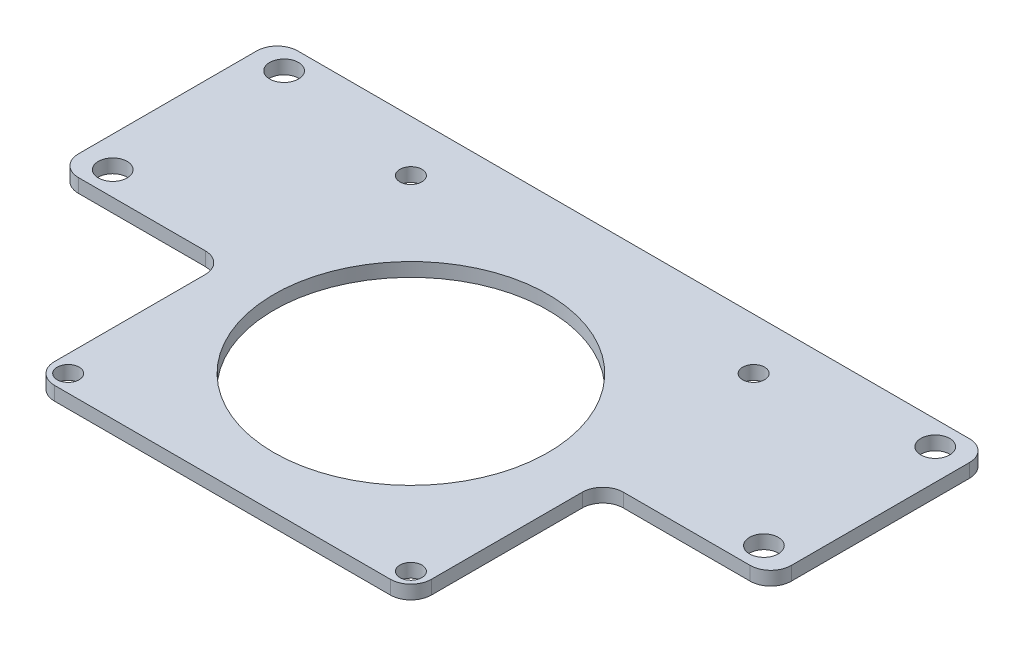
SolidWorks part; units mm, degrees
material "Thornel Mat VMA"
ref_plane "前视基准面" through (0, 0, 0) normal (0, 0, 1) x (1, 0, 0)
ref_plane "上视基准面" through (0, 0, 0) normal (0, 1, 0) x (1, 0, 0)
ref_plane "右视基准面" through (0, 0, 0) normal (1, 0, 0) x (0, 0, -1)
sketch "草图1" plane through (0, 0, 0) normal (0, 1, 0) x (1, 0, 0)
  line L0 (47.5, 12.5) -> (-47.5, 12.5) construction
  line L1 (-52, 16) -> (52, 16)
  line L2 (-52, 16) -> (-52, -16)
  line L3 (-52, -16) -> (52, -16)
  line L4 (52, 16) -> (52, -16)
  line L5 (-52, 16) -> (52, -16) construction
  line L6 (-52, -16) -> (52, 16) construction
  line L7 (0, 0) -> (0, 48.5931) construction
  line L8 (-47.5, 12.5) -> (-47.5, -12.5) construction
  line L9 (0, 0) -> (-63.5413, 0) construction
  line L10 (-25, 8.5) -> (25, 8.5) construction
  line L11 (-25, 8.5) -> (-25, -41.5) construction
  line L12 (-25, -41.5) -> (-25, -16) construction
  line L13 (-25, -41.5) -> (0, -41.5) construction
  line L14 (25, -41.5) -> (0, -41.5) construction
  line L15 (25, -41.5) -> (25, -16)
  line L16 (0, 0) -> (0, -62.887) construction
  line L17 (-27.5, -44) -> (27.5, -44)
  line L18 (-27.5, -44) -> (-27.5, -16)
  line L19 (27.5, -44) -> (27.5, -16)
  line L20 (-25, 8.5) -> (25, -41.5) construction
  circle A0 centre (-47.5, 12.5) radius 2.1
  circle A1 centre (-47.5, -12.5) radius 2.1
  circle A2 centre (-25, -41.5) radius 1.6
  circle A3 centre (-25, 8.5) radius 1.6
  circle A4 centre (25, -41.5) radius 1.6
  circle A5 centre (47.5, -12.5) radius 2.1
  circle A6 centre (25, 8.5) radius 1.6
  circle A7 centre (47.5, 12.5) radius 2.1
  circle A8 centre (0, -16.5) radius 20
  point P0 (0, 0)
  point P9 (0, 12.5)
  point P33 (0, -41.5)
  point P34 (0, -44)
  dimension "D4" = 4.2
  dimension "D6" = 4.2
  dimension "D10" = 3.2
  dimension "D11" = 3.2
  dimension "D15" = 40
  dimension "D1" = 104
  dimension "D2" = 32
  dimension "D3" = 95
  dimension "D5" = 25
  dimension "D7" = 50
  dimension "D8" = 7.5
  dimension "D9" = 50
  dimension "D12" = 55
  dimension "D13" = 2.5
  dimension "D14" = 2.5
extrude "凸台-拉伸1" add sketch "草图1" along normal blind 2 contours L4 L1 L2 L3 A6 A0 A1 A3 A5 A7 | L14 A4 L15 L3 L12 A2 L13 region at (0, 0, -14.9119) region at (-23.7469, 0, 16.6172)
fillet "圆角1" radius 3 8 edges at (52, 1, -16) (52, 1, 16) (27.5, 1, 16) (27.5, 1, 44) (-27.5, 1, 44) (-27.5, 1, 16) (-52, 1, 16) (-52, 1, -16)
